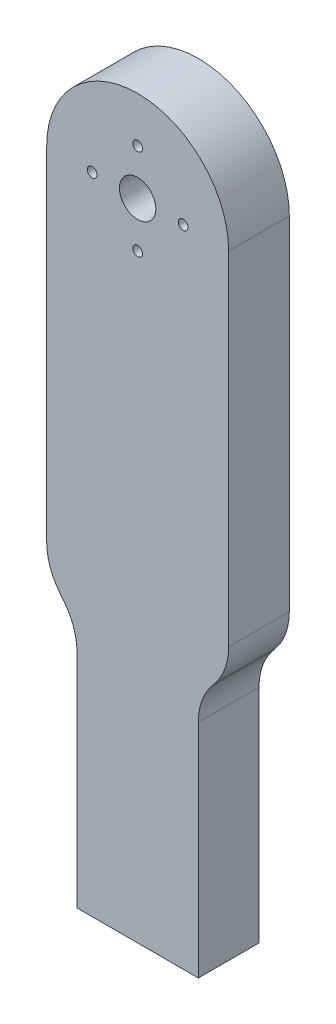
SolidWorks part; units mm, degrees
ref_plane "Plan de face" through (0, 0, 0) normal (0, 0, 1) x (1, 0, 0)
ref_plane "Plan de dessus" through (0, 0, 0) normal (0, 1, 0) x (1, 0, 0)
ref_plane "Plan de droite" through (0, 0, 0) normal (1, 0, 0) x (0, 0, -1)
sketch "Esquisse1" plane through (0, 0, 0) normal (0, 0, 1) x (1, 0, 0)
  line L0 (0, 0) -> (0, 74.7857) construction
  line L1 (-15, 13.5) -> (-15, -43.0103)
  line L2 (15, 13.5) -> (15, -43.0103)
  line L3 (-10, -92.7914) -> (10, -92.7914)
  line L24 (-12.8288, -49.232) -> (-12.1712, -50.0594)
  line L25 (-10, -56.2812) -> (-10, -92.7914)
  line L26 (10, -56.2812) -> (10, -92.7914)
  line L27 (12.8288, -49.232) -> (12.1712, -50.0594)
  circle A4 centre (-0.0053, 13.4988) radius 7.5
  arc A5 (-15, 13.5) -> (15, 13.5) centre (0, 13.5) cw
  circle A6 centre (-0.0053, 5.9988) radius 0.8
  circle A7 centre (-7.5053, 13.4988) radius 0.8
  circle A8 centre (-0.0053, 20.9988) radius 0.8
  circle A9 centre (7.4947, 13.4988) radius 0.8
  circle A10 centre (-0.0053, 13.4988) radius 3
  arc A11 (15, -43.0103) -> (12.8288, -49.232) centre (5, -43.0103) cw
  arc A12 (10, -56.2812) -> (12.1712, -50.0594) centre (20, -56.2812) cw
  arc A13 (-12.1712, -50.0594) -> (-10, -56.2812) centre (-20, -56.2812) cw
  arc A14 (-15, -43.0103) -> (-12.8288, -49.232) centre (-5, -43.0103) ccw
  point P21 (-0.0053, 13.4988)
  point P22 (-0.0053, 13.4988)
  point P24 (15, -46.5)
  point P27 (10, -52.7914)
  point P30 (-10, -52.7914)
  point P34 (-15, -46.5)
  dimension "D3" = 15
  dimension "D4" = 1.6
  dimension "D5" = 6
  dimension "D6" = 10
  dimension "D1" = 15
  dimension "D2" = 60
  dimension "D12" = 5
  dimension "D13" = 40
extrude "Boss.-Extru.1" add sketch "Esquisse1" along normal mid plane 10 contours A9 A4 A6 A7 A8 A5 L1 A14 L24 A13 L25 L3 L26 A12 L27 A11 L2 | L0 A6 A4 A9 A8 A10 | A6 L0 A10 A8 A4 A7 region at (0.0003, -31.109, 0) region at (-3.5449, 13.4988, 0) region at (3.5382, 13.4988, 0)
